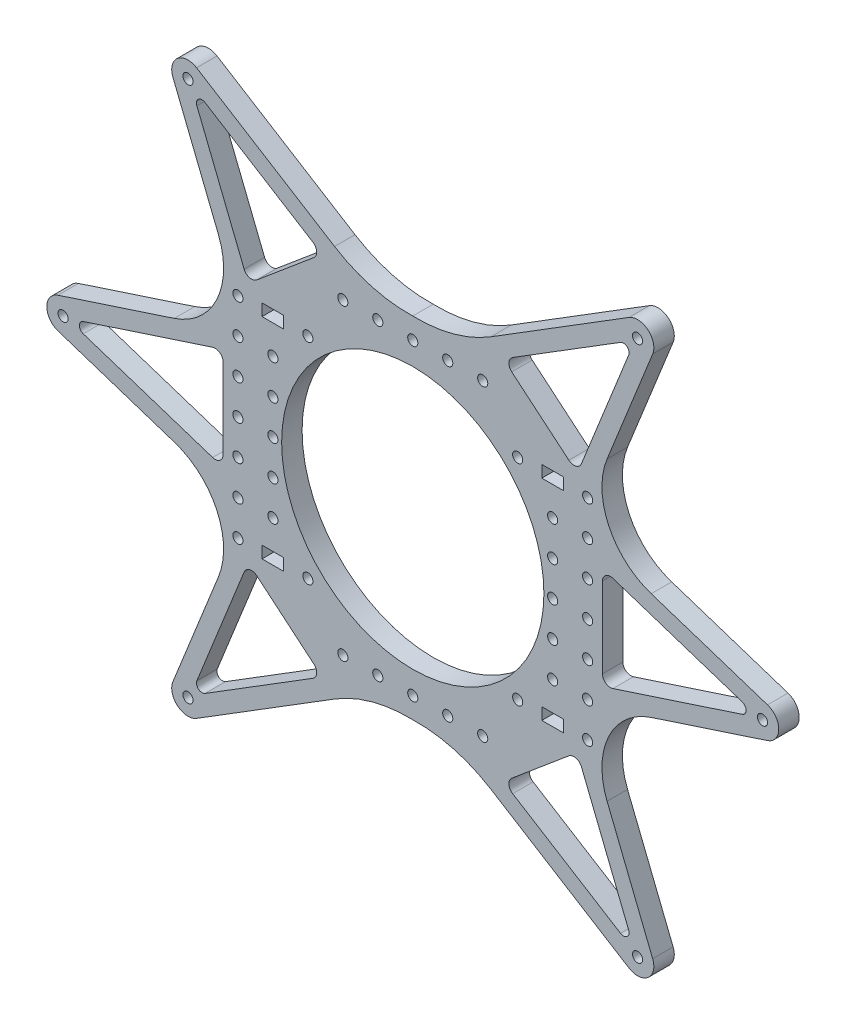
SolidWorks part; units mm, degrees
material "Acrylic (Medium-high impact)"
ref_plane "Front Plane" through (0, 0, 0) normal (0, 0, 1) x (1, 0, 0)
ref_plane "Top Plane" through (0, 0, 0) normal (0, 1, 0) x (1, 0, 0)
ref_plane "Right Plane" through (0, 0, 0) normal (1, 0, 0) x (0, 0, -1)
sketch "Sketch1" plane through (0, 0, 0) normal (0, 0, 1) x (1, 0, 0)
  line L0 (-447622.4345, 422.8828) -> (448935.6268, 422.8828) construction
  line L1 (587.9953, 497.7534) -> (601.0264, 465.2697)
  line L2 (696.5962, 452.8828) -> (696.5962, 392.8828) construction
  line L3 (653.3971, 419.0702) -> (-31485.9834, -37883.1519) construction
  line L4 (699.6962, 394.5828) -> (693.4962, 391.1828) construction
  line L5 (699.6962, 391.1828) -> (693.4962, 394.5828) construction
  line L6 (594.8522, 494.09) -> (608.3693, 460.3949)
  line L7 (594.7755, 503.4426) -> (634.2359, 478.9202)
  line L8 (597.1925, 496.0537) -> (628.0285, 476.8909)
  line L9 (594.8522, 494.09) -> (597.1925, 496.0537) construction
  line L10 (699.6962, 391.1828) -> (693.4962, 391.1828)
  line L11 (693.4962, 394.5828) -> (693.4962, 391.1828)
  line L12 (699.6962, 394.5828) -> (693.4962, 394.5828)
  line L13 (594.7755, 503.4426) -> (587.9953, 497.7534) construction
  line L14 (628.2915, 473.1954) -> (611.963, 459.4942)
  line L15 (608.3693, 460.3949) -> (628.0285, 476.8909) construction
  line L16 (699.6962, 394.5828) -> (699.6962, 391.1828)
  line L17 (-343.4038, 422.8828) -> (49656.5962, 422.8828) construction
  line L18 (648.8948, 432.061) -> (-31490.4849, 38734.2822) construction
  line L19 (-347.3366, 472.8828) -> (49652.6634, 472.8828) construction
  line L20 (-347.2527, 372.8828) -> (49652.7473, 372.8828) construction
  line L21 (562.3601, 421.3552) -> (599.3601, 409.2322)
  line L22 (602.3601, 434.3594) -> (602.3601, 411.4062)
  line L23 (555.1462, 427.3082) -> (555.1462, 418.4573) construction
  line L24 (562.3601, 424.4103) -> (599.3601, 436.5334)
  line L25 (599.3601, 409.2322) -> (599.3601, 436.5334) construction
  line L26 (555.1462, 427.3082) -> (588.4064, 438.2059)
  line L27 (562.3601, 421.3552) -> (562.3601, 424.4103) construction
  line L28 (555.1462, 418.4573) -> (588.4064, 407.5596)
  line L29 (594.8522, 351.6756) -> (608.3693, 385.3706)
  line L30 (594.7755, 342.3229) -> (634.2359, 366.8453)
  line L31 (611.963, 386.2714) -> (628.2915, 372.5702)
  line L32 (613.4962, 451.1828) -> (619.6962, 454.5828) construction
  line L33 (613.4962, 454.5828) -> (619.6962, 451.1828) construction
  line L34 (597.1925, 349.7118) -> (594.8522, 351.6756) construction
  line L35 (587.9953, 348.0122) -> (594.7755, 342.3229) construction
  line L36 (628.0285, 368.8746) -> (608.3693, 385.3706) construction
  line L37 (597.1925, 349.7118) -> (628.0285, 368.8746)
  line L38 (587.9953, 348.0122) -> (601.0264, 380.4959)
  line L39 (613.4962, 391.1828) -> (619.6962, 394.5828) construction
  line L40 (699.6962, 454.5828) -> (693.4962, 451.1828) construction
  line L41 (613.4962, 394.5828) -> (619.6962, 391.1828) construction
  line L42 (616.5962, 452.8828) -> (616.5962, 392.8828) construction
  line L43 (699.6962, 451.1828) -> (693.4962, 454.5828) construction
  line L44 (685.1639, 368.8746) -> (704.8231, 385.3706) construction
  line L45 (725.1971, 348.0122) -> (718.4169, 342.3229) construction
  line L46 (715.9998, 349.7118) -> (718.3402, 351.6756) construction
  line L47 (750.8323, 421.3552) -> (750.8323, 424.4103) construction
  line L48 (713.8323, 409.2322) -> (713.8323, 436.5334) construction
  line L49 (758.0462, 427.3082) -> (758.0462, 418.4573) construction
  line L50 (704.8231, 460.3949) -> (685.1639, 476.8909) construction
  line L51 (718.4169, 503.4426) -> (725.1971, 497.7534) construction
  line L52 (718.3402, 494.09) -> (715.9998, 496.0537) construction
  line L53 (613.4962, 454.5828) -> (619.6962, 454.5828)
  line L54 (619.6962, 451.1828) -> (619.6962, 454.5828)
  line L55 (613.4962, 451.1828) -> (619.6962, 451.1828)
  line L56 (699.6962, 451.1828) -> (699.6962, 454.5828)
  line L57 (699.6962, 451.1828) -> (693.4962, 451.1828)
  line L58 (693.4962, 451.1828) -> (693.4962, 454.5828)
  line L59 (699.6962, 454.5828) -> (693.4962, 454.5828)
  line L60 (725.1971, 348.0122) -> (712.166, 380.4959)
  line L61 (715.9998, 349.7118) -> (685.1639, 368.8746)
  line L62 (701.2294, 386.2714) -> (684.9009, 372.5702)
  line L63 (718.4169, 342.3229) -> (678.9565, 366.8453)
  line L64 (718.3402, 351.6756) -> (704.8231, 385.3706)
  line L65 (758.0462, 418.4573) -> (724.786, 407.5596)
  line L66 (758.0462, 427.3082) -> (724.786, 438.2059)
  line L67 (750.8323, 424.4103) -> (713.8323, 436.5334)
  line L68 (710.8323, 434.3594) -> (710.8323, 411.4062)
  line L69 (750.8323, 421.3552) -> (713.8323, 409.2322)
  line L70 (613.4962, 451.1828) -> (613.4962, 454.5828)
  line L71 (684.9009, 473.1954) -> (701.2294, 459.4942)
  line L72 (613.4962, 394.5828) -> (613.4962, 391.1828)
  line L73 (613.4962, 394.5828) -> (619.6962, 394.5828)
  line L74 (619.6962, 394.5828) -> (619.6962, 391.1828)
  line L75 (715.9998, 496.0537) -> (685.1639, 476.8909)
  line L76 (718.4169, 503.4426) -> (678.9565, 478.9202)
  line L77 (718.3402, 494.09) -> (704.8231, 460.3949)
  line L78 (725.1971, 497.7534) -> (712.166, 465.2697)
  line L79 (613.4962, 391.1828) -> (619.6962, 391.1828)
  line L80 (706.5962, 432.8828) -> (696.5962, 432.8828) construction
  line L81 (706.5962, 422.8828) -> (706.5962, 432.8828) construction
  line L82 (656.5962, 378.8828) -> (646.5962, 378.8828) construction
  line L83 (656.5962, 466.8828) -> (646.5962, 466.8828) construction
  line L111 (656.5962, -513.6368) -> (656.5962, 49486.3632) construction
  arc A0 (597.1925, 496.0537) -> (594.8522, 494.09) centre (596.3441, 494.6884) ccw
  arc A1 (587.9953, 497.7534) -> (594.7755, 503.4426) centre (592.3174, 499.4872) cw
  circle A2 centre (592.3174, 499.4872) radius 1.45
  arc A4 (608.3693, 460.3949) -> (611.963, 459.4942) centre (610.4925, 461.2467) ccw
  arc A5 (628.2915, 473.1954) -> (628.0285, 476.8909) centre (626.821, 474.9479) ccw
  circle A6 centre (592.3174, 499.4872) radius 4.6569 construction
  circle A7 centre (706.5962, 432.8828) radius 1.45
  circle A8 centre (706.5962, 442.8828) radius 1.45
  circle A9 centre (706.5962, 452.8828) radius 1.45
  circle A10 centre (706.5962, 392.8828) radius 1.45
  arc A11 (555.1462, 418.4573) -> (555.1462, 427.3082) centre (556.5962, 422.8828) cw
  circle A12 centre (556.5962, 422.8828) radius 1.45
  circle A13 centre (646.5962, 378.8828) radius 1.45
  circle A14 centre (556.5962, 422.8828) radius 4.6569 construction
  arc A15 (562.3601, 424.4103) -> (562.3601, 421.3552) centre (562.8606, 422.8828) ccw
  circle A16 centre (656.5962, 422.8828) radius 37.5
  circle A18 centre (636.5962, 378.8828) radius 1.45
  arc A19 (602.3601, 434.3594) -> (599.3601, 436.5334) centre (600.0724, 434.3594) ccw
  circle A20 centre (706.5962, 402.8828) radius 1.45
  arc A21 (599.3601, 409.2322) -> (602.3601, 411.4062) centre (600.0724, 411.4062) ccw
  circle A22 centre (656.5962, 466.8828) radius 1.45
  circle A23 centre (696.5962, 432.8828) radius 1.45
  circle A24 centre (592.3174, 346.2783) radius 4.6569 construction
  arc A25 (628.0285, 368.8746) -> (628.2915, 372.5702) centre (626.821, 370.8177) ccw
  arc A27 (594.7755, 342.3229) -> (587.9953, 348.0122) centre (592.3174, 346.2783) cw
  arc A28 (594.8522, 351.6756) -> (597.1925, 349.7118) centre (596.3441, 351.0771) ccw
  arc A29 (611.963, 386.2714) -> (608.3693, 385.3706) centre (610.4925, 384.5189) ccw
  circle A31 centre (592.3174, 346.2783) radius 1.45
  circle A32 centre (706.5962, 412.8828) radius 1.45
  arc A33 (588.4064, 407.5596) -> (601.0264, 380.4959) centre (582.0351, 388.1144) cw
  circle A34 centre (656.5962, 378.8828) radius 1.45
  arc A35 (588.4064, 438.2059) -> (601.0264, 465.2697) centre (582.0351, 457.6512) ccw
  circle A37 centre (696.5962, 442.8828) radius 1.45
  circle A38 centre (696.5962, 402.8828) radius 1.45
  arc A39 (634.2359, 366.8453) -> (656.5962, 372.8828) centre (655.447, 332.7133) cw
  arc A40 (634.2359, 478.9202) -> (656.5962, 472.8828) centre (655.447, 513.0523) ccw
  circle A41 centre (720.8749, 346.2783) radius 4.6569 construction
  circle A42 centre (756.5962, 422.8828) radius 4.6569 construction
  circle A43 centre (696.5962, 412.8828) radius 1.45
  circle A44 centre (646.5962, 466.8828) radius 1.45
  circle A45 centre (636.5962, 466.8828) radius 1.45
  circle A46 centre (720.8749, 499.4872) radius 4.6569 construction
  circle A47 centre (696.5962, 422.8828) radius 1.45
  circle A48 centre (676.5962, 466.8828) radius 1.45
  circle A49 centre (666.5962, 466.8828) radius 1.45
  circle A50 centre (706.5962, 422.8828) radius 1.45
  arc A51 (678.9565, 478.9202) -> (656.5962, 472.8828) centre (657.7454, 513.0523) cw
  arc A52 (678.9565, 366.8453) -> (656.5962, 372.8828) centre (657.7454, 332.7133) ccw
  circle A53 centre (686.5962, 452.8828) radius 1.45
  circle A54 centre (686.5962, 392.8828) radius 1.45
  arc A55 (724.786, 438.2059) -> (712.166, 465.2697) centre (731.1572, 457.6512) cw
  arc A56 (724.786, 407.5596) -> (712.166, 380.4959) centre (731.1572, 388.1144) ccw
  circle A57 centre (626.5962, 392.8828) radius 1.45
  circle A58 centre (720.8749, 346.2783) radius 1.45
  arc A59 (701.2294, 386.2714) -> (704.8231, 385.3706) centre (702.6999, 384.5189) cw
  arc A60 (718.3402, 351.6756) -> (715.9998, 349.7118) centre (716.8483, 351.0771) cw
  arc A61 (718.4169, 342.3229) -> (725.1971, 348.0122) centre (720.8749, 346.2783) ccw
  arc A62 (685.1639, 368.8746) -> (684.9009, 372.5702) centre (686.3714, 370.8177) cw
  arc A63 (713.8323, 409.2322) -> (710.8323, 411.4062) centre (713.12, 411.4062) cw
  arc A64 (710.8323, 434.3594) -> (713.8323, 436.5334) centre (713.12, 434.3594) cw
  circle A65 centre (676.5962, 378.8828) radius 1.45
  arc A66 (750.8323, 424.4103) -> (750.8323, 421.3552) centre (750.3318, 422.8828) cw
  circle A67 centre (666.5962, 378.8828) radius 1.45
  circle A68 centre (756.5962, 422.8828) radius 1.45
  arc A69 (758.0462, 418.4573) -> (758.0462, 427.3082) centre (756.5962, 422.8828) ccw
  circle A70 centre (626.5962, 452.8828) radius 1.45
  circle A71 centre (606.5962, 422.8828) radius 1.45
  circle A72 centre (616.5962, 422.8828) radius 1.45
  circle A73 centre (616.5962, 412.8828) radius 1.45
  arc A74 (684.9009, 473.1954) -> (685.1639, 476.8909) centre (686.3714, 474.9479) cw
  arc A75 (704.8231, 460.3949) -> (701.2294, 459.4942) centre (702.6999, 461.2467) cw
  circle A76 centre (720.8749, 499.4872) radius 1.45
  arc A77 (725.1971, 497.7534) -> (718.4169, 503.4426) centre (720.8749, 499.4872) ccw
  arc A78 (715.9998, 496.0537) -> (718.3402, 494.09) centre (716.8483, 494.6884) cw
  circle A79 centre (616.5962, 402.8828) radius 1.45
  circle A80 centre (616.5962, 442.8828) radius 1.45
  circle A81 centre (606.5962, 412.8828) radius 1.45
  circle A82 centre (616.5962, 432.8828) radius 1.45
  circle A83 centre (606.5962, 402.8828) radius 1.45
  circle A84 centre (606.5962, 392.8828) radius 1.45
  circle A85 centre (606.5962, 452.8828) radius 1.45
  circle A86 centre (606.5962, 442.8828) radius 1.45
  circle A87 centre (606.5962, 432.8828) radius 1.45
  circle A279 centre (626.5962, 466.8828) radius 1.45 [skipped]
  circle A282 centre (626.5962, 378.8828) radius 1.45 [skipped]
  point P2 (620.1272, 466.3448)
  point P4 (604.6798, 472.924)
  point P5 (610.6788, 407.5004)
  point P6 (604.4937, 430.5743)
  point P7 (590.1096, 382.987)
  point P9 (656.5962, 422.8828)
  point P10 (592.2236, 451.9603)
  point P12 (560.2236, 451.9603)
  point P13 (615.5787, 412.0526)
  point P15 (596.4648, 452.5325)
  point P16 (593.7956, 519.1439)
  point P18 (562.0153, 451.7438)
  point P19 (589.324, 503.0546)
  point P21 (557.1601, 445.912)
  point P22 (691.7574, 496.0365)
  point P23 (586.2073, 519.1355)
  point P25 (696.5962, 452.8828)
  point P27 (593.4054, 384.161)
  point P31 (706.9167, 384.1702)
  point P32 (709.3005, 386.1481)
  point P33 (712.3266, 520.5499)
  point P34 (710.2125, 451.5766)
  point P37 (593.7956, 519.1439)
  point P38 (704.5328, 382.1922)
  point P40 (675.1867, 401.4708)
  point P41 (685.2778, 409.8289)
  point P43 (705.5495, 376.706)
  point P44 (637.2651, 404.097)
  point P46 (743.1543, 445.9191)
  point P47 (656.5962, 422.8828)
  point P48 (685.1467, 493.2598)
  point P49 (742.2125, 451.5766)
  point P53 (695.1768, 484.8286)
  point P55 (708.8884, 517.1528)
  point P56 (706.5155, 519.1439)
  point P57 (714.1038, 519.1355)
  point P64 (708.6406, 384.393)
  point P66 (665.171, 499.4399)
  point P67 (704.1427, 521.135)
  point P80 (602.3601, 422.8828)
  point P86 (499.5503, 435.3778)
  point P106 (620.1272, 379.4208)
  point P114 (563.3616, 328.8714)
  point P127 (696.5962, 422.8828)
  point P143 (704.687, 438.4721)
  point P145 (738.2906, 448.6533)
  point P146 (704.7346, 451.575)
  point P147 (738.2991, 451.7509)
  point P148 (738.3077, 454.8484)
  point P244 (749.8308, 328.8714)
  point P245 (693.0651, 379.4208)
  point P246 (710.8323, 422.8828)
  point P247 (696.5962, 422.8828)
  point P248 (723.8684, 503.0546)
  point P249 (693.0651, 466.3448)
  dimension "D2" = 2.9
  dimension "D3" = 6.2644
  dimension "D6" = 4
  dimension "D9" = 4
  dimension "D7" = 4
  dimension "D11" = 100
  dimension "D12" = 5
  dimension "D19" = 50
  dimension "D20" = 100
  dimension "D25" = 6.2644
  dimension "D13" = 3
  dimension "D15" = 37
  dimension "D18" = 40
  dimension "D23" = 10
  dimension "D28" = 10
  dimension "D39" = 3.4
  dimension "D37" = 2.9
  dimension "D38" = 75
  dimension "D8" = 50
  dimension "D10" = 30
  dimension "D14" = 50
  dimension "D16" = 37
  dimension "D17" = 2
  dimension "D21" = 44
  dimension "D22" = 35
  dimension "D24" = 5
  dimension "D26" = 3
  dimension "D27" = 10
  dimension "D29" = 5
  dimension "D30" = 6.2644
  dimension "D31" = 3
  dimension "D32" = 37
  dimension "D33" = 10
  dimension "D34" = 100
  dimension "D35" = 10
  dimension "D36" = 5
  dimension "D41" = 6.2
extrude "Boss-Extrude1" add sketch "Sketch1" along normal blind 5.85
